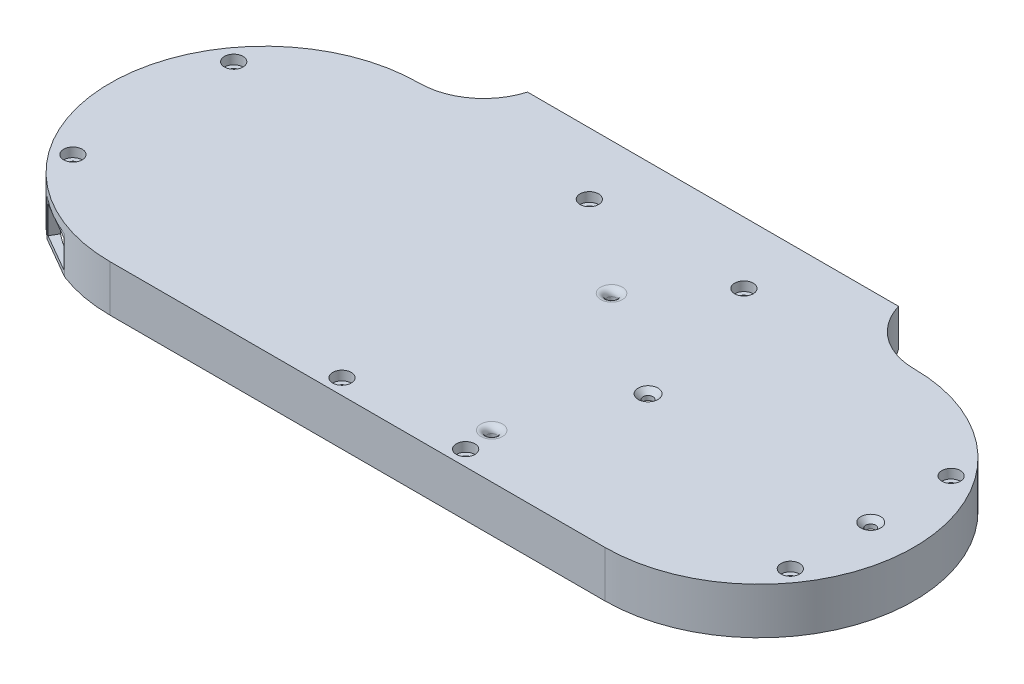
SolidWorks part; units mm, degrees
ref_plane "Front Plane" through (0, 0, 0) normal (0, 0, 1) x (1, 0, 0)
ref_plane "Top Plane" through (0, 0, 0) normal (0, 1, 0) x (1, 0, 0)
ref_plane "Right Plane" through (0, 0, 0) normal (1, 0, 0) x (0, 0, -1)
sketch "Sketch1" plane through (0, 0, 0) normal (0, 1, 0) x (1, 0, 0)
  line L0 (0, 0) -> (160, 0) construction
  line L1 (0, 50) -> (160, 50)
  line L2 (0, -50) -> (160, -50)
  arc A0 (0, 50) -> (0, -50) centre (0, 0) ccw
  arc A1 (160, -50) -> (160, 50) centre (160, 0) ccw
  point P3 (80, 0)
  dimension "D1" = 50
  dimension "D2" = 160
extrude "Boss-Extrude1" add sketch "Sketch1" against normal blind 15
shell "Shell1" thickness 3 removed face at (80, -15, 0)
sketch "Sketch2" plane through (0, 0, 0) normal (0, 1, 0) x (1, 0, 0)
  line L0 (160, 50) -> (140, 50)
  line L1 (20, 50) -> (140, 50)
  line L2 (20, 50) -> (20, 65) construction
  line L3 (20, 65) -> (140, 65)
  line L4 (140, 50) -> (140, 65) construction
  line L5 (20, 50) -> (0, 50)
  arc A0 (160, 50) -> (140, 65) centre (160, 70.8333) cw
  arc A1 (160, -50) -> (160, 50) centre (160, 0) ccw construction
  arc A2 (0, 50) -> (20, 65) centre (0, 70.8333) ccw
  arc A3 (0, 50) -> (0, -50) centre (0, 0) ccw construction
  point P9 (20, 57.5)
  dimension "D1" = 15
  dimension "D2" = 20
  dimension "D3" = 20
extrude "Boss-Extrude3" add sketch "Sketch2" against normal up to surface (15 mm away) up to face at (80, -15, 0)
chamfer "Chamfer1" distance 3 angle 45 1 edges at (80, -15, -65)
sketch "Sketch3" plane through (0, 0, -65) normal (0, 0, -1) x (-1, 0, 0)
  line L0 (-80, 0) -> (-80, 9.2744) construction
  line L1 (-140, 0) -> (-20, 0) construction
  line L2 (-80, 0) -> (-80, -2) construction
  line L3 (-89, -2) -> (-71, -2)
  line L4 (-89, -2) -> (-89, -10)
  line L5 (-89, -10) -> (-71, -10)
  line L6 (-71, -2) -> (-71, -10)
  circle A0 centre (-116, -5) radius 2.5
  circle A2 centre (-44, -5) radius 2.5
  dimension "D1" = 5
  dimension "D2" = 18
  dimension "D3" = 36
  dimension "D4" = 5
  dimension "D5" = 8
  dimension "D6" = 2
extrude "Cut-Extrude1" cut sketch "Sketch3" against normal blind 25
sketch "Sketch4" plane through (0, 0, 0) normal (1, 0, 0) x (0, 0, -1)
  line L0 (26, -3) -> (41, -3)
  line L1 (-47, -3) -> (47, -3) construction
  line L2 (41, -3) -> (35.2265, -13)
  line L3 (35.2265, -13) -> (26, -13)
  line L4 (26, -13) -> (26, -3)
  line L5 (47, -15) -> (47, -3) construction
  dimension "D1" = 15
  dimension "D2" = 60
  dimension "D3" = 10
  dimension "D4" = 6
extrude "Boss-Extrude4" add sketch "Sketch4" against normal mid plane 46
sketch "Sketch6" plane through (0, 0, -26) normal (0, 0, 1) x (1, 0, 0)
  line L0 (-23, -13) -> (23, -13) construction
  line L1 (-13, -13) -> (13, -13)
  line L2 (-13, -13) -> (-13, -3)
  line L3 (-13, -3) -> (13, -3)
  line L4 (13, -13) -> (13, -3)
  line L5 (20, 0) -> (0, 0) construction
  line L6 (-23, -3) -> (-23, -13) construction
  line L7 (23, -3) -> (23, -13) construction
  dimension "D1" = 3
  dimension "D2" = 10
  dimension "D3" = 10
extrude "Cut-Extrude2" cut sketch "Sketch6" against normal up to surface (9.2265 mm away) up to face at (-4.5957, -7.0042, -38.6882)
chamfer "Chamfer2" distance 3 angle 60 2 edges at (-18, -13, -26) (18, -13, -26) first distance on face at (-18, -13, -30.6132) first distance on face at (18, -13, -30.6132)
sketch "Sketch7" plane through (0, -18.5035, -32.049) normal (0, -0.5, -0.866) x (1, 0, 0)
  line L0 (-17, -9.9019) -> (17, -9.9019) construction
  line L1 (-13, -6.3549) -> (13, -6.3549) construction
  line L2 (0, -6.3549) -> (0, -9.9019) construction
  line L3 (23, -17.9019) -> (13, -17.9019) construction
  circle A0 centre (-17, -9.9019) radius 1.4074
  circle A1 centre (17, -9.9019) radius 1.6157
  dimension "D1" = 34
  dimension "D2" = 8
extrude "Cut-Extrude3" cut sketch "Sketch7" against normal blind 10
fillet "Fillet1" radius 6 2 edges at (-13, -3, -33.5) (13, -3, -33.5)
sketch "Sketch8" plane through (0, 0, 0) normal (1, 0, 0) x (0, 0, -1)
  line L0 (0, 0) -> (0, -8.8) construction
  line L3 (-50, -15) -> (50, -15) construction
  circle A0 centre (0, -8.8) radius 5.2
  circle A1 centre (0, -8.8) radius 6.2 construction
  dimension "D2" = 12.4
extrude "Cut-Extrude4" cut sketch "Sketch8" against normal through all
sketch "Sketch9" plane through (0, -15, 0) normal (0, -1, 0) x (1, 0, 0)
  line L0 (0, 0) -> (-25, 43.3013) construction
  line L1 (0, 0) -> (0, 50) construction
  arc A0 (0, 50) -> (0, -50) centre (0, 0) ccw construction
  dimension "D1" = 30
ref_plane "Plane1" through (-25, -15, 43.3013) normal (-0.5, 0, 0.866) x (0.866, 0, 0.5)
sketch "Sketch10" plane through (-25, -15, 43.3013) normal (-0.5, 0, 0.866) x (0.866, 0, 0.5)
  line L0 (0, 0) -> (0, 1.5) construction
  line L1 (-7, 10.5) -> (7, 10.5)
  line L2 (-7, 10.5) -> (-7, 1.5)
  line L3 (-7, 1.5) -> (7, 1.5)
  line L4 (7, 10.5) -> (7, 1.5)
  line L5 (0, 0) -> (25, 0) construction
  line L6 (-50, 0) -> (25, 0) construction
  dimension "D1" = 14
  dimension "D2" = 9
  dimension "D3" = 1.5
extrude "Cut-Extrude5" cut sketch "Sketch10" against normal blind 20
sketch "Sketch11" plane through (-25, -15, 43.3013) normal (-0.5, 0, 0.866) x (0.866, 0, 0.5)
  line L0 (0, 1.5) -> (0, 10.5) construction
  line L1 (-7.8, 12) -> (7.8, 12)
  line L2 (-7.8, 12) -> (-7.8, 0)
  line L3 (-7.8, 0) -> (7.8, 0)
  line L4 (7.8, 12) -> (7.8, 0)
  line L5 (7, 1.5) -> (-7, 1.5) construction
  line L6 (-7, 10.5) -> (7, 10.5) construction
  line L7 (0, 6) -> (7.8, 6) construction
  line L8 (0, 10.5) -> (0, 12) construction
  line L9 (0, 0) -> (25, 0) construction
  dimension "D2" = 15.6
extrude "Cut-Extrude6" cut sketch "Sketch11" against normal blind 0.6
sketch "Sketch12" plane through (0, 0, 0) normal (0, 1, 0) x (1, 0, 0)
  line L0 (0, 0) -> (200.5215, 0) construction
  circle A0 centre (196, 0) radius 1.6
  circle A1 centre (124, 0) radius 1.6
  dimension "D1" = 3.2
  dimension "D2" = 3.2
  dimension "D3" = 72
  dimension "D4" = 124
  dimension "D5" = 72
extrude "Cut-Extrude7" cut sketch "Sketch12" against normal blind 10
chamfer "Chamfer3" distance 1.6 angle 45 2 edges at (124, 0, 1.6) (196, 0, 1.6)
sketch "Sketch13" plane through (0, 0, 0) normal (0, 1, 0) x (1, 0, 0)
  line L0 (0, 0) -> (115.8356, 0) construction
  circle A0 centre (89.971, 22.211) radius 1.5
  circle A1 centre (108.933, -35.5119) radius 1.5
  dimension "D1" = 22.211
  dimension "D2" = 89.971
  dimension "D3" = 35.5119
  dimension "D4" = 108.933
extrude "Cut-Extrude8" cut sketch "Sketch13" against normal blind 5
fillet "Fillet2" radius 2 2 edges at (108.933, 0, 37.0119) (89.971, 0, -20.711)
sketch "Sketch15" plane through (0, -3, 0) normal (0, -1, 0) x (1, 0, 0)
  line L0 (68, 29) -> (112.45, 29)
  line L1 (68, 39) -> (112.45, 39)
  line L2 (68, 39) -> (68, -25.77)
  line L3 (68, -25.77) -> (112.45, -25.77)
  line L4 (112.45, 39) -> (112.45, -25.77)
  line L5 (72, 35) -> (108.45, 35)
  line L6 (72, 35) -> (72, -21.77)
  line L7 (72, -21.77) -> (108.45, -21.77)
  line L8 (108.45, 35) -> (108.45, -21.77)
  line L9 (78, 39) -> (78, -25.77)
  line L10 (102.45, 39) -> (102.45, -25.77)
  line L11 (68, -15.77) -> (112.45, -15.77)
  arc A0 (102.45, 35) -> (108.45, 29) centre (108.45, 35) ccw
  arc A1 (107.5231, 35) -> (108.45, 34.0918) centre (108.933, 35.5119) ccw
  circle A2 centre (89.971, -22.211) radius 1.5
  circle A3 centre (89.971, -22.211) radius 3.559
  circle M1 centre (89.971, -22.211) radius 1.5
  circle M2 centre (108.933, 35.5119) radius 1.5
  dimension "D1" = 4
  dimension "D2" = 4
  dimension "D3" = 4
  dimension "D4" = 4
  dimension "D5" = 10
  dimension "D6" = 10
  dimension "D7" = 10
  dimension "D8" = 10
extrude "Boss-Extrude5" add sketch "Sketch15" along normal blind 2 contours L9 L1 L2 L0 L6 L5 | L1 L10 L5 L8 L0 L4 M2 | L11 L8 L7 L10 L3 L4 | L11 L2 L3 L9 L7 L6 | A3 L7 M1 | L7 A3 M1 | L5 A0 L8 M2 region at (108.5914, -3, 31.5459) region at (105.8601, -3, 32.4099) region at (108.575, -3, -21.895) region at (71.875, -3, 35.125) region at (71.875, -3, -21.895) region at (89.971, -3, -23.7173) region at (89.971, -3, -20.3259)
sketch "Sketch18" plane through (0, -3, 0) normal (0, -1, 0) x (1, 0, 0)
  line L0 (0, 47) -> (160, 47) construction
  line L1 (55, 47) -> (60, 47)
  line L2 (55, 47) -> (55, -47)
  line L3 (55, -47) -> (60, -47)
  line L4 (60, 47) -> (60, -47)
  line L5 (160, -47) -> (0, -47) construction
  dimension "D1" = 5
  dimension "D2" = 55
extrude "Boss-Extrude6" add sketch "Sketch18" along normal blind 5
sketch "Sketch19" plane through (0, -3, 0) normal (0, -1, 0) x (1, 0, 0)
  line L0 (60, 47) -> (160, 47) construction
  line L1 (112.45, 47) -> (108.45, 47)
  line L2 (112.45, 47) -> (112.45, -47)
  line L3 (112.45, -47) -> (108.45, -47)
  line L4 (108.45, 47) -> (108.45, 36.932)
  line L5 (114.5, -47) -> (89, -47) construction
  line L6 (108.45, -15.77) -> (108.45, -21.77) construction
  line L7 (112.45, -15.77) -> (112.45, -25.77) construction
  line L8 (108.45, 34.0918) -> (108.45, -47)
  arc A0 (108.45, 34.0918) -> (108.45, 36.932) centre (108.933, 35.5119) ccw
extrude "Boss-Extrude7" add sketch "Sketch19" along normal up to surface (2 mm away) up to face at (107.7833, -5, -21.1033)
sketch "Sketch20" plane through (0, -3, 0) normal (0, -1, 0) x (1, 0, 0)
  line L0 (60, -47) -> (60, 47) construction
  line L1 (60, -47) -> (30, -47)
  line L2 (60, -47) -> (60, -17)
  line L3 (60, -17) -> (30, -17)
  line L4 (30, -47) -> (30, -17)
  dimension "D1" = 30
extrude "Boss-Extrude8" add sketch "Sketch20" along normal up to surface (12 mm away) up to face at (80, -15, 0)
fillet "Fillet3" radius 7 2 edges at (30, -15, -32) (60, -15, -32)
fillet "Fillet4" radius 12 1 edges at (42.5, -3, -17)
sketch "Sketch21" plane through (0, -3, 0) normal (0, -1, 0) x (1, 0, 0)
  line L0 (108.45, -25.77) -> (108.45, -47) construction
  line L1 (108.45, -47) -> (120.45, -47)
  line L2 (108.45, -47) -> (108.45, -25.77)
  line L3 (108.45, -25.77) -> (120.45, -25.77)
  line L4 (120.45, -47) -> (120.45, -25.77)
  line L5 (102.45, -25.77) -> (108.45, -25.77) construction
  dimension "D1" = 12
extrude "Boss-Extrude9" add sketch "Sketch21" along normal up to surface (12 mm away) up to face at (62.5, -15, -16)
sketch "Sketch16" plane through (0, 0, -65) normal (0, 0, -1) x (-1, 0, 0)
  circle A0 centre (-44, -5) radius 2.5
extrude "Cut-Extrude9" cut sketch "Sketch16" against normal blind 60
sketch "Sketch22" plane through (0, 0, -25.77) normal (0, 0, 1) x (1, 0, 0)
  line L0 (120.45, -3) -> (120.45, -7)
  line L1 (120.45, -15) -> (120.45, -3) construction
  line L2 (120.45, -7) -> (115.45, -10)
  line L3 (115.45, -10) -> (115.45, -15)
  line L4 (108.45, -15) -> (120.45, -15) construction
  line L5 (115.45, -15) -> (120.45, -15)
  line L6 (120.45, -15) -> (120.45, -7)
  line L7 (120.45, -3) -> (112.45, -3) construction
  line M9 (108.45, -15) -> (120.45, -15)
  line M10 (120.45, -15) -> (120.45, -3)
  dimension "D1" = 4
  dimension "D2" = 5
  dimension "D3" = 5
extrude "Cut-Extrude10" cut sketch "Sketch22" against normal up to surface (21.23 mm away) contours L2 L3 M9 M10 region at (118.1423, -11.6923, -25.77) up to face at (140.225, -9, -47)
fillet "Fillet5" radius 5 2 edges at (115.45, -10, -36.385) (120.45, -7, -36.385)
sketch "Sketch23" plane through (0, 0, -65) normal (0, 0, -1) x (-1, 0, 0)
  circle A0 centre (-116, -5) radius 2.5
extrude "Cut-Extrude11" cut sketch "Sketch23" against normal up to surface (39.23 mm away) up to face at (114.95, -8, -25.77)
sketch "Sketch25" plane through (0, -15, 0) normal (0, -1, 0) x (1, 0, 0)
  line L4 (75.7511, 47.0333) -> (64.2489, 47.0333)
  line L6 (115.6569, 47) -> (104.3431, 47)
  line L7 (0, 0) -> (160, 0) construction
  line L9 (0, -47) -> (160, -47)
  line L10 (160, -50) -> (0, -50)
  line L11 (0, 50) -> (160, 50)
  arc A0 (160, -50) -> (160, 50) centre (160, 0) ccw
  arc A1 (0, 50) -> (0, -50) centre (0, 0) ccw
  arc A19 (160, -47) -> (160, 47) centre (160, 0) ccw construction
  arc A20 (160, -47) -> (160, 47) centre (160, 0) ccw
  arc A23 (0, -47) -> (-23, 40.9878) centre (0, 0) cw
  circle A24 centre (-36, 26) radius 1.6
  arc A25 (-34.5812, 31.8298) -> (-41.0881, 22.8203) centre (-36, 26) cw
  circle A26 centre (-36, -26) radius 1.6
  arc A27 (-41.0881, -22.8203) -> (-34.5812, -31.8298) centre (-36, -26) cw
  circle A28 centre (60, -45) radius 1.6
  arc A29 (54.3431, -47) -> (65.6569, -47) centre (60, -45) cw
  circle A30 centre (70, 45) radius 1.5
  arc A31 (75.7511, 47.0333) -> (64.2489, 47.0333) centre (70, 45) cw
  circle A32 centre (110, 45) radius 1.6
  arc A33 (115.6569, 47) -> (104.3431, 47) centre (110, 45) cw
  circle A34 centre (110, -45) radius 1.6
  arc A35 (104.3431, -47) -> (115.6569, -47) centre (110, -45) cw
  circle A36 centre (196, 26) radius 1.6
  arc A37 (201.0881, 22.8203) -> (194.5812, 31.8298) centre (196, 26) cw
  circle A38 centre (196, -26) radius 1.6
  arc A39 (194.5812, -31.8298) -> (201.0881, -22.8203) centre (196, -26) cw
  line M13 (115.45, -47) -> (115.45, -25.77)
  line M15 (108.45, -25.77) -> (108.45, -47)
  line M16 (108.45, -47) -> (53, -47)
  line M22 (0, 47) -> (160, 47)
  dimension "D1" = 6.1
extrude "Boss-Extrude10" add sketch "Sketch25" against normal up to surface (12 mm away) contours A37 A20 A36 | A29 L9 A28 | A25 A23 A24 | A27 A23 A26 | A39 A20 A38 | A35 A34 M16 M15 | A35 A34 L9 M15 M13 | A35 L9 M13 | A31 A30 M22 | A32 | A33 L6 region at (-37.9705, -15, 27.4231) region at (-37.9705, -15, -27.4231) region at (60, -15, -43.3252) region at (115.6755, -15, -44.9337) region at (197.9705, -15, -27.4231) region at (197.9705, -15, 27.4231) region at (70, -15, 43.3064) region at (112.0436, -15, -43.0153) region at (106.4966, -15, -43.6958) region at (110, -15, 45) up to face at (196, -3, 1.6)
fillet "Fillet6" radius 5 15 edges at (108.45, -9, -39.2037) (104.3431, -9, -47) (65.6569, -9, -47) (-34.5812, -9, -31.8298) (-41.0881, -9, -22.8203) (-34.5812, -9, 31.8298) (-41.0881, -9, 22.8203) (64.2372, -9, 47) (104.3431, -9, 47) (75.7628, -9, 47) (115.6569, -9, 47) (201.0881, -9, -22.8203) (194.5812, -9, -31.8298) (194.5812, -9, 31.8298) (201.0881, -9, 22.8203)
sketch "Sketch26" plane through (0, -15, 0) normal (0, -1, 0) x (1, 0, 0)
  arc A0 (108.45, 44.6031) -> (108.45, 45.3969) centre (110, 45) ccw construction
  circle A1 centre (70, 45) radius 1.5 construction
  arc A2 (108.45, 44.6031) -> (108.45, 45.3969) centre (110, 45) ccw
  circle A3 centre (70, 45) radius 1.5
  circle A4 centre (196, -26) radius 1.6 construction
  circle A5 centre (196, 26) radius 1.6 construction
  circle A6 centre (196, -26) radius 1.6
  circle A7 centre (196, 26) radius 1.6
  circle A8 centre (60, -45) radius 1.6 construction
  circle A9 centre (60, -45) radius 1.6
  circle A10 centre (110, -45) radius 1.6
  circle A11 centre (-36, -26) radius 1.6 construction
  circle A12 centre (-36, 26) radius 1.6
  circle A13 centre (-36, 26) radius 1.6
  circle A14 centre (-36, -26) radius 1.6
  arc A15 (108.45, 45.3969) -> (108.45, 44.6031) centre (110, 45) ccw construction
  arc A16 (108.45, 45.3969) -> (108.45, 44.6031) centre (110, 45) ccw
  dimension "D1" = 3.2
  dimension "D2" = 0
extrude "Cut-Extrude12" cut sketch "Sketch26" against normal through all
sketch "Sketch27" plane through (0, 0, 0) normal (0, 1, 0) x (1, 0, 0)
  circle A0 centre (-36, 26) radius 3
  circle A1 centre (-36, -26) radius 3
  circle A2 centre (70, -45) radius 3
  circle A3 centre (110, -45) radius 3
  circle A4 centre (196, -26) radius 3
  circle A5 centre (196, 26) radius 3
  circle A6 centre (110, 45) radius 3
  circle A7 centre (60, 45) radius 3
  dimension "D1" = 6
  dimension "D2" = 6
  dimension "D3" = 6
  dimension "D4" = 6
  dimension "D5" = 6
  dimension "D6" = 6
  dimension "D7" = 6
  dimension "D8" = 6
extrude "Cut-Extrude13" cut sketch "Sketch27" against normal blind 3
